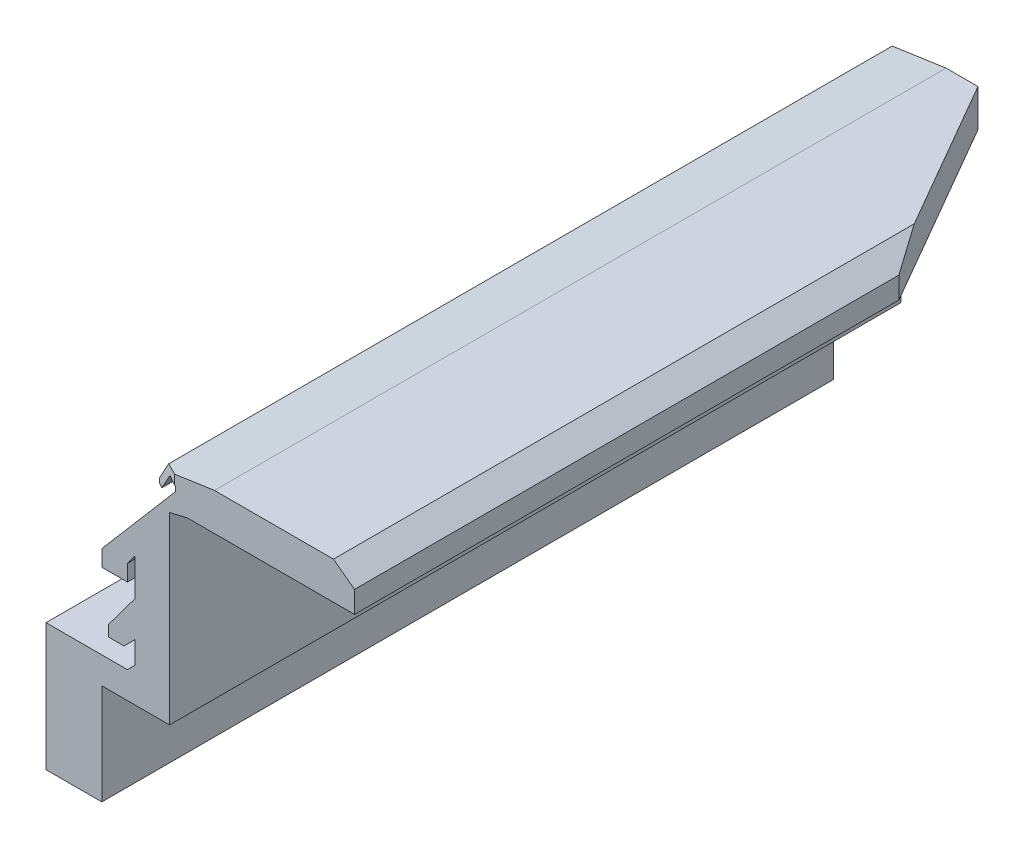
SolidWorks part; units mm, degrees
ref_plane "Спереди" through (0, 0, 0) normal (0, 0, 1) x (1, 0, 0)
ref_plane "Сверху" through (0, 0, 0) normal (0, 1, 0) x (1, 0, 0)
ref_plane "Справа" through (0, 0, 0) normal (1, 0, 0) x (0, 0, -1)
sketch "Эскиз1" plane through (0, 0, 1548) normal (0, 0, 1) x (1, 0, 0)
  line L0 (36.5493, 66.5695) -> (29.833, 66.5695)
  line L1 (816.0298, -10.4848) -> (838.0298, -10.4848) construction
  line L2 (29.833, 66.5695) -> (29.833, 81.8912)
  line L3 (29.833, 81.8912) -> (39.6289, 81.8912)
  line L4 (39.6289, 81.8912) -> (40.5498, 82.8122)
  line L5 (40.5498, 82.8122) -> (40.5498, 85.4913)
  line L6 (40.5498, 85.4913) -> (39.2102, 84.1517)
  line L7 (39.2102, 84.1517) -> (37.3683, 84.1517)
  line L8 (37.3683, 84.1517) -> (37.3683, 85.4913)
  line L9 (37.3683, 85.4913) -> (40.5498, 89.7613)
  line L10 (40.5498, 89.7613) -> (40.5498, 94.1987)
  line L11 (40.5498, 94.1987) -> (39.6289, 92.9627)
  line L12 (39.6289, 92.9627) -> (39.6289, 91.0172)
  line L13 (39.6289, 91.0172) -> (36.5493, 91.0172)
  line L14 (36.5493, 91.0172) -> (36.5493, 92.9627)
  line L15 (36.5493, 92.9627) -> (45.4059, 103.3248)
  line L16 (45.4059, 103.3248) -> (45.4059, 103.9108)
  line L17 (45.4059, 103.9108) -> (43.9825, 103.9108)
  line L18 (43.9825, 103.9108) -> (41.6607, 100.7946)
  line L19 (41.6607, 100.7946) -> (40.9776, 100.7946)
  line L20 (40.9776, 100.7946) -> (40.9776, 101.3036)
  line L21 (40.9776, 101.3036) -> (43.6205, 104.8507)
  line L22 (43.6205, 104.8507) -> (50.1002, 105.7972)
  line L23 (50.1002, 105.7972) -> (64.4114, 105.7972)
  line L24 (64.4114, 105.7972) -> (66.9431, 103.9108)
  line L25 (66.9431, 103.9108) -> (66.9431, 101.3036)
  line L26 (66.9431, 101.3036) -> (46.8604, 101.3036)
  line L27 (46.8604, 101.3036) -> (44.6942, 100.7946)
  line L28 (44.6942, 100.7946) -> (44.6942, 78.6678)
  line L29 (44.6942, 78.6678) -> (36.5493, 78.6678)
  line L30 (36.5493, 78.6678) -> (36.5493, 66.5695)
  dimension "D1" = 22
extrude "Бобышка-Вытянуть1" add sketch "Эскиз1" along normal blind 88
chamfer "Фаска1" distance 13 angle 60 1 edges at (66.9431, 102.6072, 1548) first distance on face at (42.9191, 92.2024, 1548)
chamfer "Фаска2" distance 2.5 angle 60 1 edges at (40.9776, 101.0491, 1636) first distance on face at (40.9776, 101.0491, 1592)
